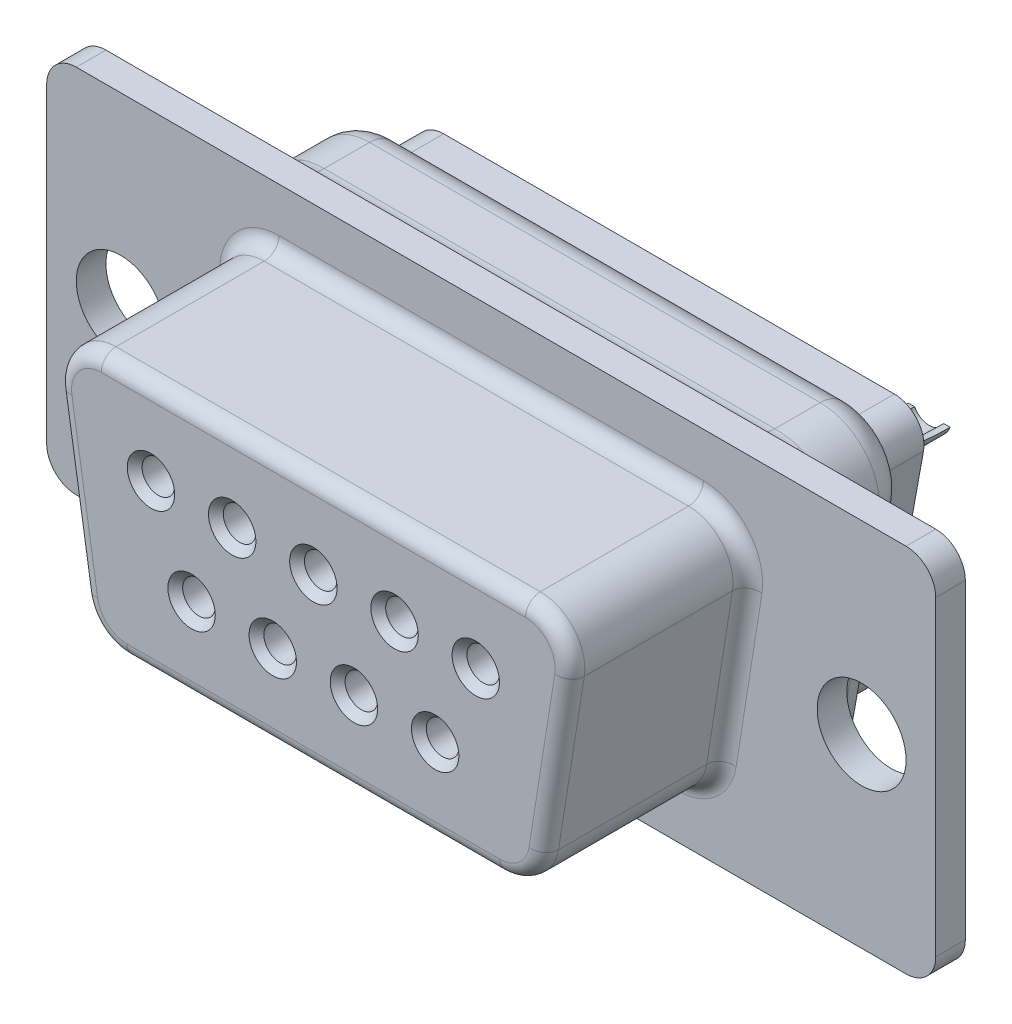
SolidWorks part; units mm, degrees
ref_plane "Спереди" through (0, 0, 0) normal (0, 0, 1) x (1, 0, 0)
ref_plane "Сверху" through (0, 0, 0) normal (0, 1, 0) x (1, 0, 0)
ref_plane "Справа" through (0, 0, 0) normal (1, 0, 0) x (0, 0, -1)
sketch "Эскиз1" plane through (0, 0, 0) normal (0, 0, 1) x (1, 0, 0)
  line L1 (-15, 6.25) -> (15, 6.25)
  line L2 (-15, 6.25) -> (-15, -6.25)
  line L3 (-15, -6.25) -> (15, -6.25)
  line L4 (15, 6.25) -> (15, -6.25)
  line L5 (-15, 6.25) -> (15, -6.25) construction
  line L6 (-15, -6.25) -> (15, 6.25) construction
  point P0 (0, 0)
  dimension "D1" = 30
  dimension "D2" = 12.5
extrude "Бобышка-Вытянуть1" add sketch "Эскиз1" along normal mid plane 1
sketch "Эскиз2" plane through (0, 0, -0.5) normal (0, 0, -1) x (-1, 0, 0)
  line L0 (0, 5.5) -> (0, -5.5) construction
  line L1 (-7.6036, 5.5) -> (7.6036, 5.5)
  line L2 (-9.5713, 3.1422) -> (-8.2986, -3.8578)
  line L3 (-6.3308, -5.5) -> (6.3308, -5.5)
  line L4 (9.5713, 3.1422) -> (8.2986, -3.8578)
  arc A0 (6.3308, -5.5) -> (8.2986, -3.8578) centre (6.3308, -3.5) ccw
  arc A1 (-8.2986, -3.8578) -> (-6.3308, -5.5) centre (-6.3308, -3.5) ccw
  arc A2 (7.6036, 5.5) -> (9.5713, 3.1422) centre (7.6036, 3.5) cw
  arc A3 (-7.6036, 5.5) -> (-9.5713, 3.1422) centre (-7.6036, 3.5) ccw
  point P0 (0, 0)
  point P10 (8, -5.5)
  point P13 (-8, -5.5)
  point P16 (10, 5.5)
  point P19 (-10, 5.5)
  dimension "D4" = 2
  dimension "D1" = 11
  dimension "D2" = 20
  dimension "D3" = 16
extrude "Бобышка-Вытянуть2" add sketch "Эскиз2" along normal blind 3.5
sketch "Эскиз3" plane through (0, 0, -4) normal (0, 0, -1) x (-1, 0, 0)
  line L0 (7.3147, -3.6789) -> (8.5874, 3.3211)
  line L1 (7.6036, 4.5) -> (-7.6036, 4.5)
  line L2 (-8.5874, 3.3211) -> (-7.3147, -3.6789)
  line L3 (-6.3308, -4.5) -> (6.3308, -4.5)
  line L4 (8.2986, -3.8578) -> (9.5713, 3.1422)
  line L5 (7.6036, 5.5) -> (-7.6036, 5.5)
  line L6 (-9.5713, 3.1422) -> (-8.2986, -3.8578)
  line L7 (-6.3308, -5.5) -> (6.3308, -5.5)
  line L8 (8.2986, -3.8578) -> (9.5713, 3.1422) construction
  line L9 (7.6036, 5.5) -> (-7.6036, 5.5) construction
  line L10 (-9.5713, 3.1422) -> (-8.2986, -3.8578) construction
  line L11 (-6.3308, -5.5) -> (6.3308, -5.5) construction
  arc A0 (8.5874, 3.3211) -> (7.6036, 4.5) centre (7.6036, 3.5) ccw
  arc A1 (-7.6036, 4.5) -> (-8.5874, 3.3211) centre (-7.6036, 3.5) ccw
  arc A2 (-7.3147, -3.6789) -> (-6.3308, -4.5) centre (-6.3308, -3.5) ccw
  arc A3 (6.3308, -4.5) -> (7.3147, -3.6789) centre (6.3308, -3.5) ccw
  arc A4 (6.3308, -5.5) -> (8.2986, -3.8578) centre (6.3308, -3.5) ccw
  arc A5 (9.5713, 3.1422) -> (7.6036, 5.5) centre (7.6036, 3.5) ccw
  arc A6 (-7.6036, 5.5) -> (-9.5713, 3.1422) centre (-7.6036, 3.5) ccw
  arc A7 (-8.2986, -3.8578) -> (-6.3308, -5.5) centre (-6.3308, -3.5) ccw
  arc A8 (6.3308, -5.5) -> (8.2986, -3.8578) centre (6.3308, -3.5) ccw construction
  arc A9 (9.5713, 3.1422) -> (7.6036, 5.5) centre (7.6036, 3.5) ccw construction
  arc A10 (-7.6036, 5.5) -> (-9.5713, 3.1422) centre (-7.6036, 3.5) ccw construction
  arc A11 (-8.2986, -3.8578) -> (-6.3308, -5.5) centre (-6.3308, -3.5) ccw construction
  dimension "D1" = 0
  dimension "D2" = 1
extrude "Бобышка-Вытянуть3" add sketch "Эскиз3" along normal blind 1.5
sketch "Эскиз4" plane through (0, 0, -5.5) normal (0, 0, -1) x (-1, 0, 0)
  circle A0 centre (-5.48, 1.42) radius 0.75
  circle A1 centre (-5.48, 1.42) radius 0.55
  dimension "D1" = 1.5
  dimension "D2" = 0.2
  dimension "D4" = 5.48
  dimension "D3" = 1.42
extrude "Бобышка-Вытянуть4" add sketch "Эскиз4" along normal blind 3.3
sketch "Эскиз5" plane through (0, 0, 0) normal (1, 0, 0) x (0, 0, -1)
  line L0 (8.8, 0.67) -> (8.8, 2.17) construction
  ellipse E0 centre (8.8, 2.17) end of major axis (11.3, 2.17) minor radius 1
  dimension "D1" = 2.5
  dimension "D2" = 1
extrude "Вырез-Вытянуть1" cut sketch "Эскиз5" along normal through all
pattern_linear "Линейный массив1" count 5 spacing 2.74 along (-1, 0, 0) of "Бобышка-Вытянуть4", "Вырез-Вытянуть1"
sketch "Эскиз6" plane through (0, 0, -5.5) normal (0, 0, -1) x (-1, 0, 0)
  circle A0 centre (-4.11, -1.42) radius 0.75
  circle A1 centre (-4.11, -1.42) radius 0.55
  circle A2 centre (-5.48, 1.42) radius 0.75 construction
  circle A3 centre (-5.48, 1.42) radius 0.55 construction
  dimension "D1" = 1.42
  dimension "D2" = 4.11
extrude "Бобышка-Вытянуть5" add sketch "Эскиз6" along normal blind 3.3
sketch "Эскиз7" plane through (0, 0, 0) normal (1, 0, 0) x (0, 0, -1)
  line L0 (8.8, -2.17) -> (8.8, -0.67) construction
  ellipse E0 centre (8.8, -2.17) end of major axis (6.3, -2.17) minor radius 1
  dimension "D1" = 1
extrude "Вырез-Вытянуть2" cut sketch "Эскиз7" along normal through all
pattern_linear "Линейный массив2" count 4 spacing 2.74 along (-1, 0, 0) of "Бобышка-Вытянуть5", "Вырез-Вытянуть2"
sketch "Эскиз8" plane through (0, 0, 0.5) normal (0, 0, 1) x (1, 0, 0)
  line L0 (-12.5, 0) -> (12.5, 0) construction
  circle A0 centre (-12.5, 0) radius 1.5
  circle A1 centre (12.5, 0) radius 1.5
  dimension "D2" = 3
  dimension "D1" = 25
extrude "Вырез-Вытянуть3" cut sketch "Эскиз8" against normal through all
fillet "Скругление1" radius 1 4 edges at (15, -6.25, 0) (-15, -6.25, 0) (-15, 6.25, 0) (15, 6.25, 0)
fillet "Скругление2" radius 1 14 edges at (9.1391, 4.7815, -4) (0, 5.5, -4) (-9.1391, 4.7815, -4) (-8.935, -0.3578, -4) (-7.6123, -5.0355, -4) (0, -5.5, -4) (7.6123, -5.0355, -4) (-9.1391, 4.7815, -0.5) (-8.935, -0.3578, -0.5) (-7.6123, -5.0355, -0.5) (7.6123, -5.0355, -0.5) (8.935, -0.3578, -0.5) (9.1391, 4.7815, -0.5) (8.935, -0.3578, -4)
sketch "Эскиз9" plane through (0, 0, 0.5) normal (0, 0, 1) x (1, 0, 0)
  line L0 (0, 4.75) -> (0, -4.75) construction
  line L1 (-7.1594, 4.75) -> (7.1594, 4.75) construction
  line L2 (-9.135, 2.4381) -> (-8.2665, -3.0619) construction
  line L3 (-6.291, -4.75) -> (6.291, -4.75) construction
  line L4 (9.135, 2.4381) -> (8.2665, -3.0619) construction
  line L5 (-7.1594, 4.25) -> (7.1594, 4.25)
  line L6 (8.6411, 2.5161) -> (7.7727, -2.9839)
  line L7 (-6.291, -4.25) -> (6.291, -4.25)
  line L8 (-8.6411, 2.5161) -> (-7.7727, -2.9839)
  arc A0 (6.291, -4.75) -> (8.2665, -3.0619) centre (6.291, -2.75) ccw construction
  arc A1 (-8.2665, -3.0619) -> (-6.291, -4.75) centre (-6.291, -2.75) ccw construction
  arc A2 (7.1594, 4.75) -> (9.135, 2.4381) centre (7.1594, 2.75) cw construction
  arc A3 (-7.1594, 4.75) -> (-9.135, 2.4381) centre (-7.1594, 2.75) ccw construction
  arc A4 (7.1594, 4.25) -> (8.6411, 2.5161) centre (7.1594, 2.75) cw
  arc A5 (6.291, -4.25) -> (7.7727, -2.9839) centre (6.291, -2.75) ccw
  arc A6 (-7.7727, -2.9839) -> (-6.291, -4.25) centre (-6.291, -2.75) ccw
  arc A7 (-7.1594, 4.25) -> (-8.6411, 2.5161) centre (-7.1594, 2.75) ccw
  point P0 (0, 0)
  point P10 (8, -4.75)
  point P13 (-8, -4.75)
  point P16 (9.5, 4.75)
  point P19 (-9.5, 4.75)
  dimension "D4" = 2
  dimension "D1" = 19
  dimension "D2" = 16
  dimension "D3" = 9.5
  dimension "D5" = 0.5
extrude "Бобышка-Вытянуть6" add sketch "Эскиз9" along normal blind 6
sketch "Эскиз10" plane through (0, 0, 0.5) normal (0, 0, 1) x (1, 0, 0)
  circle A0 centre (5.48, 1.42) radius 0.55
  circle A1 centre (2.74, 1.42) radius 0.55
  circle A2 centre (0, 1.42) radius 0.55
  circle A3 centre (-2.74, 1.42) radius 0.55
  circle A4 centre (-5.48, 1.42) radius 0.55
  circle A5 centre (-4.11, -1.42) radius 0.55
  circle A6 centre (-1.37, -1.42) radius 0.55
  circle A7 centre (1.37, -1.42) radius 0.55
  circle A8 centre (4.11, -1.42) radius 0.55
  circle A9 centre (5.48, 1.42) radius 0.55 construction
extrude "Вырез-Вытянуть5" cut sketch "Эскиз10" along normal through all
fillet "Скругление3" radius 0.5 16 edges at (8.2998, 3.7244, 6.5) (8.2069, -0.2339, 6.5) (7.2655, -3.8904, 6.5) (0, -4.25, 6.5) (-7.2655, -3.8904, 6.5) (-8.2069, -0.2339, 6.5) (-8.2998, 3.7244, 6.5) (8.2998, 3.7244, 0.5) (8.2069, -0.2339, 0.5) (7.2655, -3.8904, 0.5) (0, -4.25, 0.5) (-7.2655, -3.8904, 0.5) (-8.2069, -0.2339, 0.5) (-8.2998, 3.7244, 0.5) (0, 4.25, 6.5) (0, 4.25, 0.5)
chamfer "Фаска1" distance 0.25 angle 45 9 edges at (4.66, -1.42, 6.5) (-0.82, -1.42, 6.5) (-4.93, 1.42, 6.5) (0.55, 1.42, 6.5) (6.03, 1.42, 6.5) (3.29, 1.42, 6.5) (-2.19, 1.42, 6.5) (-3.56, -1.42, 6.5) (1.92, -1.42, 6.5)
